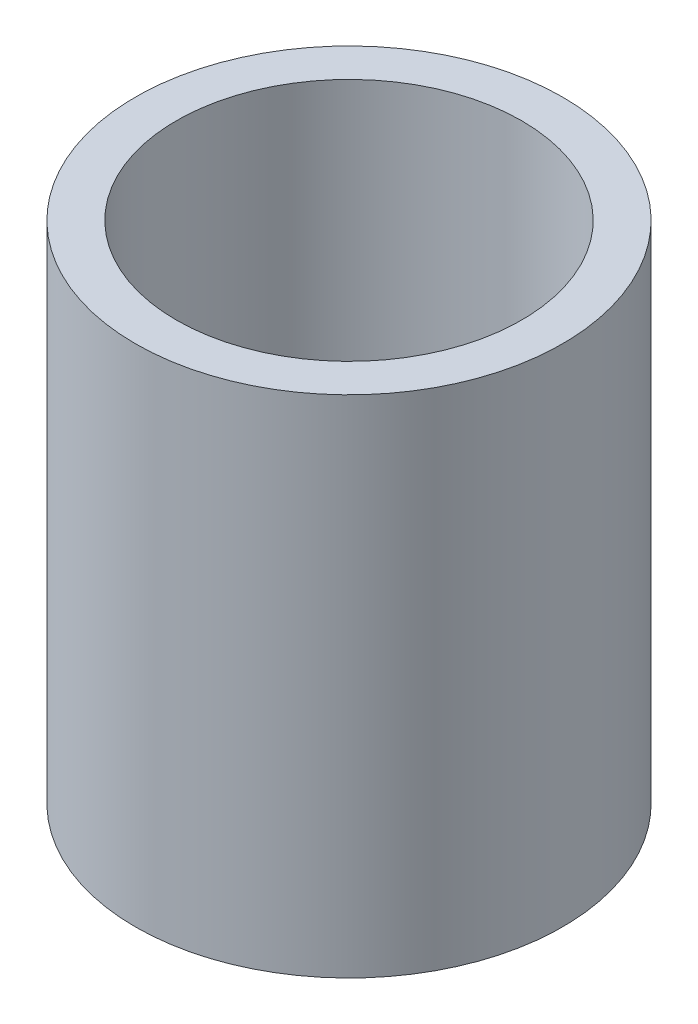
SolidWorks part; units mm, degrees
ref_plane "Front Plane" through (0, 0, 0) normal (0, 0, 1) x (1, 0, 0)
ref_plane "Top Plane" through (0, 0, 0) normal (0, 1, 0) x (1, 0, 0)
ref_plane "Right Plane" through (0, 0, 0) normal (1, 0, 0) x (0, 0, -1)
sketch "Sketch1" plane through (0, 0, 0) normal (0, 1, 0) x (1, 0, 0)
  circle A0 centre (0, 0) radius 6.325
  circle A1 centre (0, 0) radius 7.825
  point P6 (4.915, 0.3052)
  dimension "D1" = 1.5
  dimension "D2" = 12.65
extrude "Boss-Extrude1" add sketch "Sketch1" along normal blind 12.75
extrude "Boss-Extrude2" add sketch "Sketch1<2>" against normal blind 5.75 contours A1
sketch "Sketch1<2>" plane through (0, 0, 0) normal (0, 1, 0) x (1, 0, 0) same geometry as "Sketch1"
sketch "Sketch2" plane through (0, -5.75, 0) normal (0, -1, 0) x (1, 0, 0)
  line L0 (-2, 0) -> (2, 0) construction
  line L5 (-2, 1.525) -> (2, 1.525)
  line L6 (-2, -1.525) -> (2, -1.525)
  arc A0 (-2, 1.525) -> (-2, -1.525) centre (-2, 0) ccw
  arc A1 (2, -1.525) -> (2, 1.525) centre (2, 0) ccw
  point P2 (0, 0)
  dimension "D1" = 4
  dimension "D2" = 3.05
extrude "Cut-Extrude1" cut sketch "Sketch2" against normal blind 5.75
